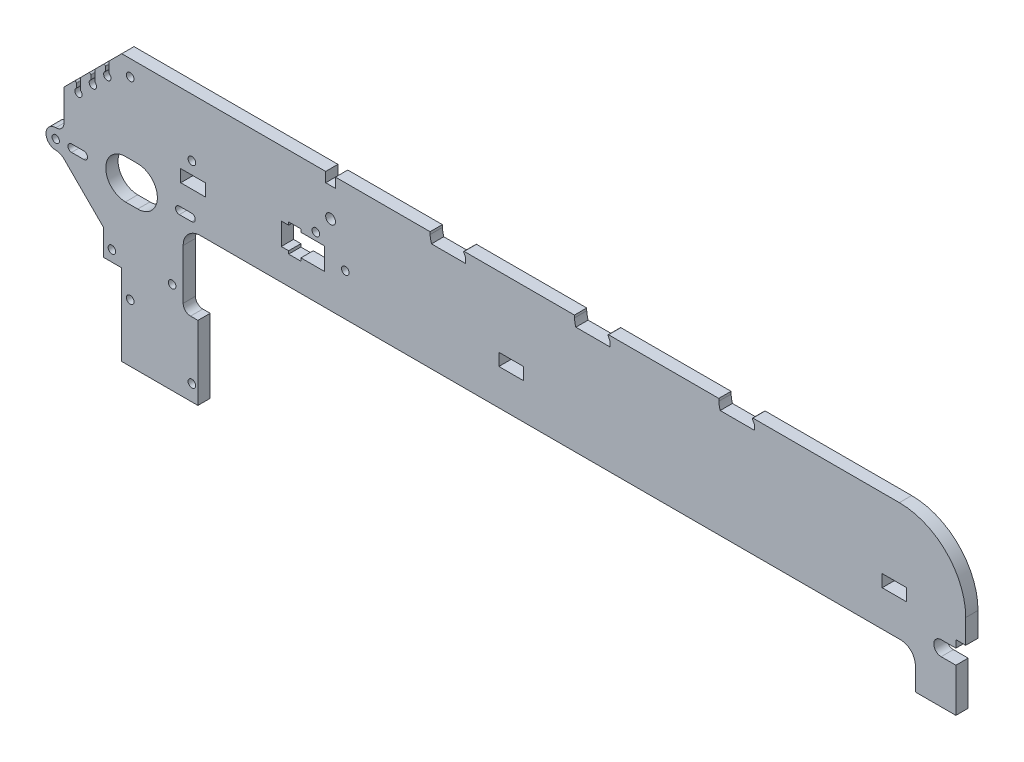
SolidWorks part; units mm, degrees
material "6061-T6 Black anodised"
ref_plane "Front Plane" through (0, 0, 0) normal (0, 0, 1) x (1, 0, 0)
ref_plane "Top Plane" through (0, 0, 0) normal (0, 1, 0) x (1, 0, 0)
ref_plane "Right Plane" through (0, 0, 0) normal (1, 0, 0) x (0, 0, -1)
sketch "Sketch1" plane through (0, 0, 0) normal (0, 0, 1) x (1, 0, 0)
  line L0 (-19.5, 0) -> (36.1968, 0) construction
  line L1 (-1.5, 32) -> (20.5, 32) construction
  line L2 (-21.9203, 0) -> (-30, 0) construction
  line L3 (-6.5, 43.5) -> (-6.5, 28.8553) construction
  line L4 (-1.5, 43.5) -> (20.5, 43.5) construction
  line L5 (310, 43.5) -> (250.4045, 43.5)
  line L6 (21.9203, 0) -> (0, 21.9203) construction
  line L7 (0, 21.9203) -> (-21.9203, 0) construction
  line L8 (-21.9203, 0) -> (0, -21.9203) construction
  line L9 (0, -21.9203) -> (21.9203, 0) construction
  line L10 (316.5, -4.6) -> (316.5, -20)
  line L11 (-6.5, -65) -> (-6.5, -32)
  line L12 (-30, 5.3553) -> (-30, -5.3553) construction
  line L13 (327, 3.7) -> (333, 3.7)
  line L14 (316.5, -20) -> (333, -20)
  line L15 (18.5, -4.6) -> (316.5, -4.6)
  line L16 (34.5, -11.1) -> (59.432, -11.1) construction
  line L17 (333, 6.7) -> (333, 3.7)
  line L18 (9.5, 43.5) -> (9.5, -35.4767) construction
  line L19 (-1.5, 43.5) -> (20.5, 43.5) construction
  line L20 (-1.5, 43.5) -> (-1.5, 20.5) construction
  line L21 (-6.5, -65) -> (24.5, -65)
  line L22 (-1.5, 20.5) -> (20.5, 20.5) construction
  line L23 (327, -2.3) -> (333, -2.3)
  line L24 (333, -2.3) -> (333, -20)
  line L25 (333, 6.7) -> (337, 6.7)
  line L26 (337, 6.7) -> (337, 16.5)
  line L27 (18.5, -35) -> (18.5, -4.6)
  line L28 (20.5, 43.5) -> (20.5, 20.5) construction
  line L29 (17.5, 15) -> (17.5, 10)
  line L30 (17.5, 15) -> (27.5, 15)
  line L31 (27, 72.5933) -> (67, 72.5933) construction
  line L32 (147, 10) -> (157, 10)
  line L33 (147, 10) -> (147, 15)
  line L34 (17.5, 10) -> (27.5, 10)
  line L35 (27.5, 15) -> (27.5, 10)
  line L36 (147, 15) -> (157, 15)
  line L37 (157, 10) -> (157, 15)
  line L38 (303, 10) -> (313, 10)
  line L39 (303, 10) -> (303, 15)
  line L40 (303, 15) -> (313, 15)
  line L41 (313, 10) -> (313, 15)
  line L42 (27, 72.5933) -> (27, -81.6129) construction
  line L43 (27, -81.6129) -> (67, -81.6129) construction
  line L44 (67, 72.5933) -> (67, -81.6129) construction
  line L45 (-1.5, -52.5) -> (20.5, -52.5) construction
  line L46 (-1.5, -65) -> (20.5, -65) construction
  line L47 (-1.5, -65) -> (-1.5, -42) construction
  line L48 (-1.5, -42) -> (20.5, -42) construction
  line L49 (20.5, -65) -> (20.5, -42) construction
  line L50 (58.4277, 8) -> (61.4277, 8)
  line L51 (27.5, 12.5) -> (63.9277, 12.5) construction
  line L52 (61.4277, 6.8061) -> (66.4277, 6.8061)
  line L53 (61.4277, 6.8061) -> (61.4277, 8)
  line L54 (76, 8) -> (76, 17)
  line L55 (72.5, 20.1) -> (72.5, 7.1) construction
  line L56 (66.4277, 6.8061) -> (66.4277, 8)
  line L57 (66.4277, 8) -> (76, 8)
  line L58 (63.9277, 12.5) -> (76, 12.5) construction
  line L59 (66.4277, 18.1939) -> (61.4277, 18.1939)
  line L60 (66.4277, 6.8061) -> (61.4277, 18.1939) construction
  line L61 (61.4277, 6.8061) -> (66.4277, 18.1939) construction
  line L62 (18.5, -35) -> (24.5, -35)
  line L63 (66.4277, 17) -> (66.4277, 18.1939)
  line L64 (66.4277, 17) -> (76, 17)
  line L65 (61.4277, 17) -> (61.4277, 18.1939)
  line L66 (24.5, -35) -> (24.5, -65)
  line L67 (-14, -21.3553) -> (-30, -5.3553)
  line L68 (-14, -21.3553) -> (-14, -32)
  line L69 (-14, -32) -> (-6.5, -32)
  line L70 (119, 43.5) -> (119, 42.5)
  line L71 (119.5675, 39.5) -> (133.5, 39.5)
  line L72 (177.75, 43.5) -> (177.75, 42.5)
  line L73 (119, 43.5) -> (80.5, 43.5)
  line L74 (-6.5, 28.8553) -> (-30, 5.3553) construction
  line L75 (178.3175, 39.5) -> (192.25, 39.5)
  line L76 (159.788, -14) -> (-14, -14) construction
  line L77 (159.788, -14) -> (159.788, -26) construction
  line L78 (61.4277, 17) -> (58.4277, 17)
  line L79 (159.788, -26) -> (-14, -26) construction
  line L80 (-14, -14) -> (-14, -26) construction
  line L81 (58.4277, 17) -> (58.4277, 8)
  line L82 (159.788, -14) -> (-14, -26) construction
  line L83 (159.788, -26) -> (-14, -14) construction
  line L84 (192.25, 39.5) -> (192.25, 41.5)
  line L85 (192.25, 41.5) -> (191.4309, 43.1382)
  line L86 (236.5, 43.5) -> (236.5, 42.5)
  line L87 (237.0675, 39.5) -> (251, 39.5)
  line L88 (251, 39.5) -> (251, 41.5)
  line L89 (177.75, 43.5) -> (132.9045, 43.5)
  line L90 (251, 41.5) -> (250.1809, 43.1382)
  line L91 (-33.3631, 8.7185) -> (-33.3631, -8.7185) construction
  line L92 (76.5, 27.7514) -> (80.5, 27.7514) construction
  line L93 (133.5, 39.5) -> (133.5, 41.5)
  line L94 (76.5, 43.5) -> (76.5, 39.5)
  line L95 (76.5, 39.5) -> (80.5, 39.5)
  line L96 (80.5, 43.5) -> (80.5, 39.5)
  line L97 (76.5, 43.5) -> (-6.5, 43.5)
  line L98 (-30, 20) -> (-6.5, 43.5)
  line L99 (-30, 20) -> (-30, 7.3254)
  line L100 (133.5, 41.5) -> (132.6809, 43.1382)
  line L101 (119, 43.5) -> (177.75, 43.5) construction
  line L102 (191.6545, 43.5) -> (236.5, 43.5)
  circle A0 centre (9.5, 34.5) radius 1.55 construction
  circle A1 centre (0, 0) radius 15.5 construction
  circle A2 centre (0, 21.9203) radius 1.5 construction
  circle A3 centre (21.9203, 0) radius 1.5
  circle A4 centre (0, -21.9203) radius 1.5 construction
  circle A5 centre (-21.9203, 0) radius 1.5
  circle A6 centre (0, 0) radius 5.5 construction
  arc A7 (337, 16.5) -> (310, 43.5) centre (310, 16.5) ccw
  circle A8 centre (0, 0) radius 8
  circle A9 centre (-3.05, 37) radius 1.55
  circle A10 centre (9.5, -57) radius 1.55 construction
  arc A11 (327, 3.7) -> (327, -2.3) centre (327, 0.7) ccw
  circle A12 centre (72, 0.4) radius 5 construction
  circle A13 centre (22, 38.5) radius 5 construction
  circle A14 centre (22, 38.5) radius 1.5 construction
  circle A15 centre (72, 0.4) radius 1.5 construction
  circle A16 centre (22.05, 20) radius 1.55
  circle A17 centre (-3.05, -41.5) radius 1.55
  circle A18 centre (22.05, -58.5) radius 1.55
  circle A19 centre (81.5, 20.1) radius 1.55 construction
  circle A20 centre (72.5, 20.1) radius 1.55
  circle A21 centre (84.5, 12.5) radius 1.55
  circle A22 centre (-10.5, -27.55) radius 1.55
  arc A23 (-33.3631, 3.9623) -> (-33.3631, -3.9623) centre (-33.3631, 0) ccw
  circle A24 centre (14, -27.55) radius 1.55
  circle A25 centre (-33.3631, 0) radius 1.5
  arc A26 (-33.3631, 3.9623) -> (-30, 7.3254) centre (-33.3631, 7.3254) ccw
  arc A27 (-33.3631, -3.9623) -> (-30, -5.3553) centre (-33.3631, -8.7185) cw
  circle A28 centre (78.5, 27.7514) radius 2
  arc A29 (119, 42.5) -> (119.5675, 39.5) centre (132.5, 43.5) ccw
  arc A30 (132.9045, 43.5) -> (132.6809, 43.1382) centre (132.9045, 43.25) ccw
  arc A31 (177.75, 42.5) -> (178.3175, 39.5) centre (191.25, 43.5) ccw
  arc A32 (191.6545, 43.5) -> (191.4309, 43.1382) centre (191.6545, 43.25) ccw
  arc A33 (236.5, 42.5) -> (237.0675, 39.5) centre (250, 43.5) ccw
  arc A34 (250.4045, 43.5) -> (250.1809, 43.1382) centre (250.4045, 43.25) ccw
  point P18 (26.8692, -2.8293)
  point P19 (26.8692, 2.8293)
  point P108 (58.4277, 12.5)
  point P115 (72.894, -20)
  dimension "D2" = 31
  dimension "D3" = 3
  dimension "D4" = 11
  dimension "D12" = 16
  dimension "D20" = 3.1
  dimension "D22" = 8
  dimension "D25" = 3
  dimension "D28" = 6
  dimension "D32" = 10
  dimension "D38" = 3
  dimension "D14" = 31
  dimension "D41" = 3.1
  dimension "D44" = 9
  dimension "D45" = 3.1
  dimension "D53" = 6
  dimension "D18" = 7.5
  dimension "D57" = 3.1
  dimension "D69" = 4
  dimension "D65" = 0.5
  dimension "D7" = 9
  dimension "D11" = 16.5
  dimension "D17" = 15
  dimension "D8" = 65
  dimension "D9" = 43.5
  dimension "D5" = 9.5
  dimension "D6" = 4.6
  dimension "D10" = 6.5
  dimension "D13" = 337
  dimension "D15" = 23
  dimension "D16" = 25
  dimension "D19" = 30
  dimension "D21" = 9
  dimension "D23" = 21.1
  dimension "D24" = 15.4
  dimension "D26" = 6
  dimension "D27" = 4
  dimension "D29" = 67
  dimension "D30" = 17.5
  dimension "D31" = 40
  dimension "D33" = 5
  dimension "D34" = 10
  dimension "D35" = 24
  dimension "D36" = 180
  dimension "D37" = 22
  dimension "D39" = 5
  dimension "D40" = 12
  dimension "D42" = 11
  dimension "D43" = 6
  dimension "D46" = 3.1
  dimension "D47" = 9
  dimension "D48" = 15
  dimension "D49" = 0.7
  dimension "D50" = 5
  dimension "D51" = 12
  dimension "D52" = 3.5
  dimension "D54" = 4
  dimension "D55" = 12
  dimension "D56" = 20
  dimension "D58" = 4.5
  dimension "D59" = 3
  dimension "D60" = 9
  dimension "D61" = 30
  dimension "D62" = 12.5
  dimension "D63" = 1
  dimension "D64" = 14.5
  dimension "D66" = 1
  dimension "D68" = 4
  dimension "D70" = 6
  dimension "D71" = 2
  dimension "D72" = 58.75
  dimension "D67" = 3
extrude "Boss-Extrude1" add sketch "Sketch1" along normal blind 5
fillet "Fillet1" [suppressed] radius 8
fillet "Fillet2" radius 7 1 edges at (18.5, -4.6, 2.5)
fillet "Fillet3" radius 3 1 edges at (18.5, -35, 2.5)
sketch "Sketch2" plane through (0, 0, 5) normal (0, 0, 1) x (1, 0, 0)
  line L0 (21.9203, 0) -> (16.9203, 0) construction
  line L1 (21.9203, -1.5) -> (16.9203, -1.5)
  line L2 (21.9203, 1.5) -> (16.9203, 1.5)
  line L3 (0, 0) -> (-5, 0) construction
  line L4 (0, -8) -> (-5, -8)
  line L5 (0, 8) -> (-5, 8)
  line L6 (-21.9203, 0) -> (-26.9203, 0) construction
  line L7 (-21.9203, -1.5) -> (-26.9203, -1.5)
  line L8 (-21.9203, 1.5) -> (-26.9203, 1.5)
  arc A0 (21.9203, -1.5) -> (21.9203, 1.5) centre (21.9203, 0) ccw
  arc A1 (16.9203, 1.5) -> (16.9203, -1.5) centre (16.9203, 0) ccw
  arc A2 (0, -8) -> (0, 8) centre (0, 0) ccw
  arc A3 (-5, 8) -> (-5, -8) centre (-5, 0) ccw
  arc A4 (-21.9203, -1.5) -> (-21.9203, 1.5) centre (-21.9203, 0) ccw
  arc A5 (-26.9203, 1.5) -> (-26.9203, -1.5) centre (-26.9203, 0) ccw
  circle A6 centre (21.9203, 0) radius 1.5 construction
  circle A7 centre (0, 0) radius 8 construction
  point P4 (19.4203, 0)
  point P9 (-2.5, 0)
  point P16 (-24.4203, 0)
  dimension "D1" = 5
extrude "Cut-Extrude1" cut sketch "Sketch2" against normal through all
fillet "Fillet4" radius 6 1 edges at (316.5, -4.6, 2.5)
sketch "Sketch3" plane through (0, 0, 5) normal (0, 0, 1) x (1, 0, 0)
  line L0 (-12.375, 32.625) -> (-12.375, 37.625) construction
  line L1 (-13.125, 42.8359) -> (-11.625, 42.8359)
  line L2 (-13.125, 42.8359) -> (-13.125, 33.924)
  line L3 (-6.5, 43.5) -> (-30, 20) construction
  line L4 (-11.625, 42.8359) -> (-11.625, 33.924)
  line L5 (-13.125, 42.8359) -> (-11.625, 33.924) construction
  line L6 (-13.125, 33.924) -> (-11.625, 42.8359) construction
  line L7 (-6.5, 43.5) -> (-12.375, 37.625) construction
  line L8 (-12.375, 37.625) -> (-18.25, 31.75) construction
  line L9 (-18.25, 31.75) -> (-24.125, 25.875) construction
  line L10 (-24.125, 25.875) -> (-30, 20) construction
  line L11 (-17.4, 36.9218) -> (-17.4, 27.9859)
  line L12 (-18.25, 26.75) -> (-18.25, 31.75) construction
  line L13 (-19.1, 36.9218) -> (-17.4, 27.9859) construction
  line L14 (-19.1, 27.9859) -> (-17.4, 36.9218) construction
  line L15 (-19.1, 36.9218) -> (-19.1, 27.9859)
  line L16 (-19.1, 36.9218) -> (-17.4, 36.9218)
  line L17 (-23.275, 31.0468) -> (-23.275, 22.1109)
  line L18 (-24.975, 31.0468) -> (-23.275, 22.1109) construction
  line L19 (-24.975, 22.1109) -> (-23.275, 31.0468) construction
  line L20 (-24.975, 31.0468) -> (-23.275, 31.0468)
  line L21 (-24.125, 20.875) -> (-24.125, 25.875) construction
  line L22 (-24.975, 31.0468) -> (-24.975, 22.1109)
  arc A0 (-13.125, 33.924) -> (-11.625, 33.924) centre (-12.375, 32.625) ccw
  arc A1 (-19.1, 27.9859) -> (-17.4, 27.9859) centre (-18.25, 26.75) ccw
  arc A2 (-24.975, 22.1109) -> (-23.275, 22.1109) centre (-24.125, 20.875) ccw
  point P0 (-12.375, 38.3799)
  point P15 (-18.25, 32.4539)
  point P22 (-24.125, 26.5789)
  dimension "D1" = 1.5
  dimension "D2" = 1.5
  dimension "D3" = 5
extrude "Cut-Extrude2" cut sketch "Sketch3" against normal through all
fillet "Fillet5" radius 0.5 3 edges at (-24.975, 25.025, 2.5) (-19.1, 30.9, 2.5) (-13.125, 36.875, 2.5)
equation "\"y-plate-thickness\"=5"
equation "\"bed-plate-thickness\"=3"
equation "\"x-plate-thickness\"=5"
equation "\"D1@Boss-Extrude1\"=\"x-plate-thickness\""
equation "\"D33@Sketch1\"=\"x-plate-thickness\""
